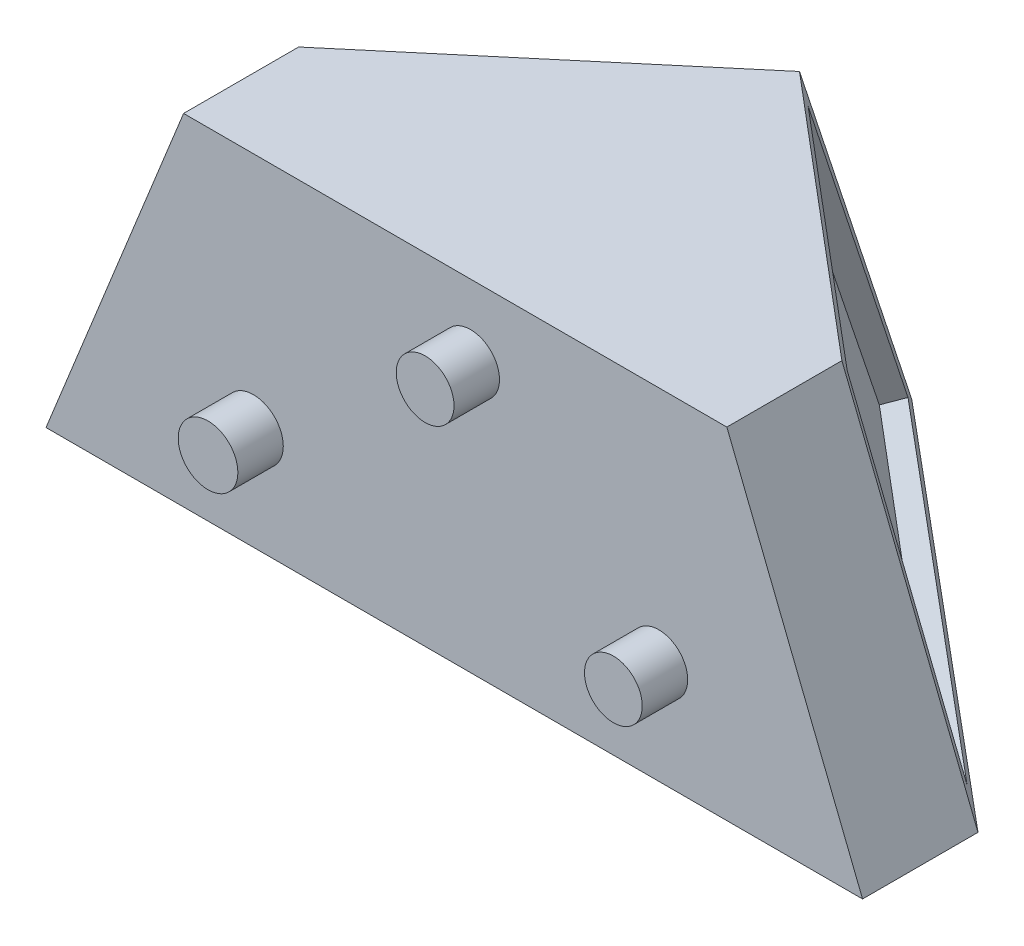
SolidWorks part; units mm, degrees
ref_plane "Front Plane" through (0, 0, 0) normal (0, 0, 1) x (1, 0, 0)
ref_plane "Top Plane" through (0, 0, 0) normal (0, 1, 0) x (1, 0, 0)
ref_plane "Right Plane" through (0, 0, 0) normal (1, 0, 0) x (0, 0, -1)
sketch "Sketch1" plane through (0, 0, 0) normal (0, 1, 0) x (1, 0, 0)
  line L0 (-35.7209, -19.8317) -> (9.9158, -19.8317)
  line L1 (9.9158, -19.8317) -> (9.9158, -13.3804)
  line L3 (-35.7209, -13.3804) -> (-35.7209, -19.8317)
  line L5 (-12.9026, 5.7345) -> (-35.7209, -13.3804)
  line L6 (-12.9026, 5.7345) -> (9.9158, -13.3804)
ref_plane "Plane2" through (0, 0, 0) normal (0, 1, 0) x (1, 0, 0)
ref_plane "Plane3" through (0, 19.05, 0) normal (0, 1, 0) x (1, 0, 0)
sketch "Sketch7" plane through (0, 19.05, 0) normal (0, 1, 0) x (1, 0, 0)
  line L2 (2.3299, -19.8317) -> (-28.0309, -19.8317)
  line L3 (-28.0309, -19.8317) -> (-28.0309, -13.402)
  line L4 (-28.0309, -13.402) -> (-12.8505, -0.5911)
  line L5 (-12.8505, -0.5911) -> (2.3299, -13.402)
  line L6 (2.3299, -13.402) -> (2.3299, -19.8317)
loft "Loft1" add profiles "Sketch7", "Sketch1" connector at (-28.0309, 19.05, 13.402) connector at (-35.7209, 0, 13.3804)
sketch "Sketch8" plane through (0, 0, 19.8317) normal (0, 0, 1) x (1, 0, 0)
  circle A0 centre (-11.9912, 14.9931) radius 1.6144
  circle A1 centre (-1.4717, 5.7234) radius 1.6144
  circle A2 centre (-24.1251, 5.7234) radius 1.6665
extrude "Boss-Extrude1" add sketch "Sketch8" along normal blind 2.54
ref_plane "Plane5" through (-2.3167, -0.9256, 2.7452) normal (0.6245, 0.2495, -0.7401) x (-0.781, 0.1995, -0.5918)
sketch "Sketch10" plane through (-2.3167, -0.9256, 2.7452) normal (0.6245, 0.2495, -0.7401) x (-0.781, 0.1995, -0.5918)
  line L0 (-5.3257, 21.0436) -> (-13.739, 5.0283)
  line L1 (-13.739, 5.0283) -> (12.3593, -0.4808)
  line L2 (12.3593, -0.4808) -> (12.3593, 17.3676)
  line L3 (12.3593, 17.3676) -> (-5.3257, 21.0436)
extrude "Cut-Extrude1" cut sketch "Sketch10" against normal blind 1.27
ref_plane "Plane7" through (-7.7353, 3.133, -9.1661) normal (-0.624, 0.2527, -0.7394) x (-0.7814, -0.2018, 0.5905)
sketch "Sketch14" plane through (-7.7353, 3.133, -9.1661) normal (-0.624, 0.2527, -0.7394) x (-0.7814, -0.2018, 0.5905)
  line L0 (34.1017, 5.2496) -> (25.2619, 21.5743)
  line L1 (25.2619, 21.5743) -> (7.4775, 17.7166)
  line L2 (7.4775, 17.7166) -> (7.4775, -0.5255)
  line L3 (7.4775, -0.5255) -> (34.1017, 5.2496)
extrude "Cut-Extrude3" cut sketch "Sketch14" against normal blind 1.27 contours L2 L3 L0 L1
shell "Shell1" thickness 2.54 removed face at (-12.9026, 0, 12.138)
